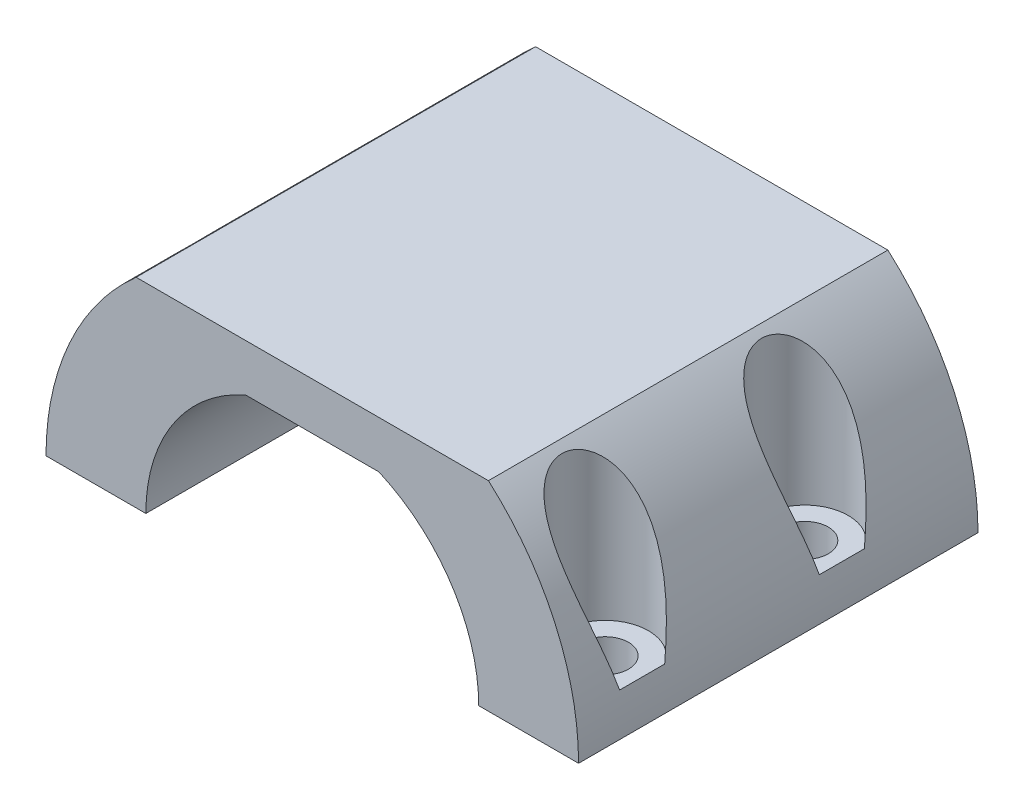
SolidWorks part; units mm, degrees
ref_plane "Front Plane" through (0, 0, 0) normal (0, 0, 1) x (1, 0, 0)
ref_plane "Top Plane" through (0, 0, 0) normal (0, 1, 0) x (1, 0, 0)
ref_plane "Right Plane" through (0, 0, 0) normal (1, 0, 0) x (0, 0, -1)
sketch "Sketch1" plane through (0, 0, 0) normal (0, 0, 1) x (1, 0, 0)
  line L0 (-20, 0) -> (-12.5, 0)
  line L1 (12.5, 0) -> (20, 0)
  line L2 (-5, 11.4564) -> (5, 11.4564)
  arc A0 (12.5, 0) -> (5, 11.4564) centre (0, 0) ccw
  arc A1 (20, 0) -> (-20, 0) centre (0, 0) ccw
  arc A2 (-5, 11.4564) -> (-12.5, 0) centre (0, 0) ccw
  dimension "D1" = 25
  dimension "D2" = 40
  dimension "D3" = 10
extrude "Boss-Extrude1" add sketch "Sketch1" along normal blind 30
sketch "Sketch2" plane through (0, 0, 0) normal (0, 1, 0) x (1, 0, 0)
  line L0 (0, 0) -> (0, -30) construction
  line L1 (-17, -25) -> (17, -25) construction
  line L2 (-17, -25) -> (-17, -10) construction
  line L3 (-17, -10) -> (17, -10) construction
  line L4 (17, -25) -> (17, -10) construction
  line L5 (-17, -25) -> (17, -10) construction
  line L6 (-17, -10) -> (17, -25) construction
  line L7 (-20, -30) -> (20, -30) construction
  line L8 (0, -30) -> (0, 0) construction
  circle A0 centre (-17, -10) radius 1.75
  circle A1 centre (17, -10) radius 1.75
  circle A2 centre (17, -25) radius 1.75
  circle A3 centre (-17, -25) radius 1.75
  point P0 (0, -17.5)
  dimension "D3" = 3.5
  dimension "D1" = 15
  dimension "D2" = 34
  dimension "D4" = 5
extrude "Cut-Extrude2" cut sketch "Sketch2" along normal through all
ref_plane "Plane1" through (0, 3, 0) normal (0, 1, 0) x (1, 0, 0)
sketch "Sketch4" plane through (0, 3, 0) normal (0, 1, 0) x (1, 0, 0)
  circle A0 centre (17, -10) radius 1.75 construction
  circle A2 centre (17, -25) radius 1.75 construction
  circle A3 centre (-17, -25) radius 1.75 construction
  circle A5 centre (-17, -10) radius 1.75 construction
  circle A30 centre (17, -10) radius 1.75
  circle A32 centre (17, -25) radius 1.75
  circle A33 centre (-17, -25) radius 1.75
  circle A35 centre (-17, -10) radius 1.75
  circle A36 centre (17, -10) radius 3.25
  circle A38 centre (17, -25) radius 3.25
  circle A39 centre (-17, -25) radius 3.25
  circle A41 centre (-17, -10) radius 3.25
  dimension "D1" = 1.5
extrude "Cut-Extrude3" cut sketch "Sketch4" along normal through all
sketch "Sketch5" plane through (0, 0, 30) normal (0, 0, 1) x (1, 0, 0)
  line L1 (-16.8059, 25) -> (16.8059, 25)
  line L2 (-16.8059, 25) -> (-16.8059, 15)
  line L3 (-16.8059, 15) -> (16.8059, 15)
  line L4 (16.8059, 25) -> (16.8059, 15)
  line L5 (-16.8059, 25) -> (16.8059, 15) construction
  line L6 (-16.8059, 15) -> (16.8059, 25) construction
  arc A0 (20, 0) -> (-20, 0) centre (0, 0) ccw construction
  point P0 (0, 20)
  dimension "10" = 10
extrude "Cut-Extrude4" cut sketch "Sketch5" against normal through all
